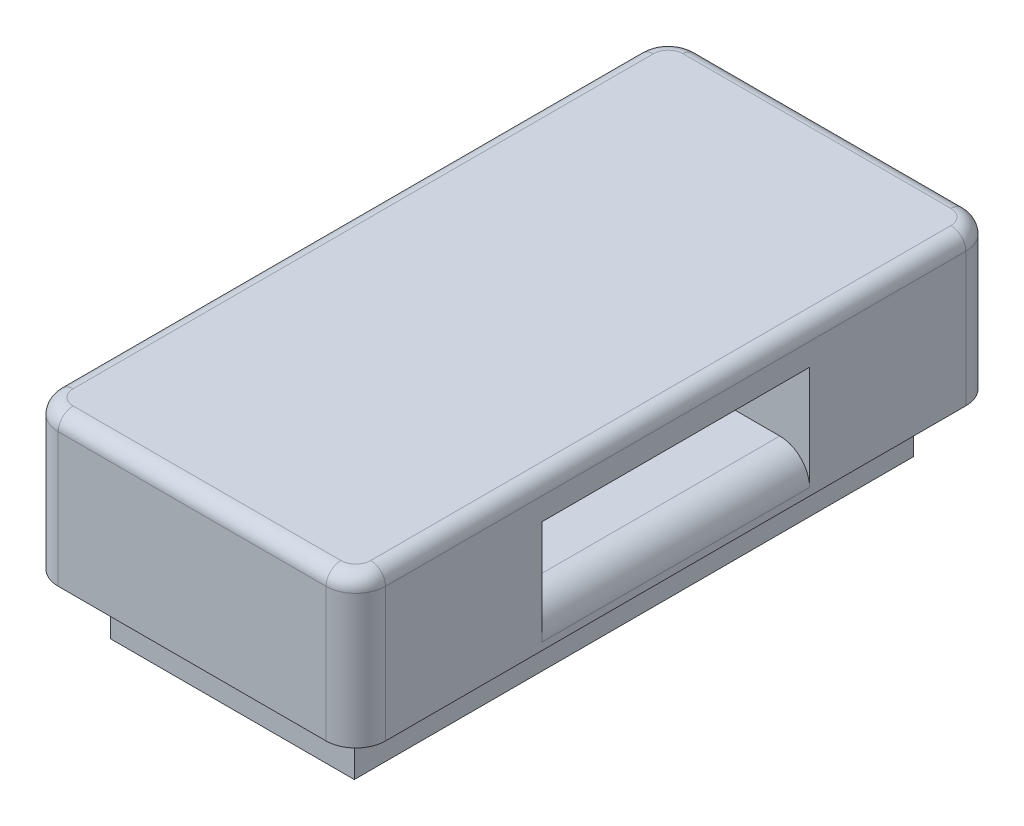
SolidWorks part; units mm, degrees
ref_plane "Front Plane" through (0, 0, 0) normal (0, 0, 1) x (1, 0, 0)
ref_plane "Top Plane" through (0, 0, 0) normal (0, 1, 0) x (1, 0, 0)
ref_plane "Right Plane" through (0, 0, 0) normal (1, 0, 0) x (0, 0, -1)
sketch "Sketch1" plane through (0, 0, 0) normal (0, 1, 0) x (1, 0, 0)
  line L1 (8.2, -18.8) -> (-8.2, -18.8)
  line L2 (8.2, -18.8) -> (8.2, 18.8)
  line L3 (8.2, 18.8) -> (-8.2, 18.8)
  line L4 (-8.2, -18.8) -> (-8.2, 18.8)
  line L5 (8.2, -18.8) -> (-8.2, 18.8) construction
  line L6 (8.2, 18.8) -> (-8.2, -18.8) construction
  line L7 (-9, -21.5) -> (9, -21.5)
  line L8 (-11, -19.5) -> (-11, 19.5)
  line L9 (-9, 21.5) -> (9, 21.5)
  line L10 (11, -19.5) -> (11, 19.5)
  line L11 (-11, -21.5) -> (11, 21.5) construction
  line L12 (-11, 21.5) -> (11, -21.5) construction
  arc A0 (-9, -21.5) -> (-11, -19.5) centre (-9, -19.5) cw
  arc A1 (9, -21.5) -> (11, -19.5) centre (9, -19.5) ccw
  arc A2 (9, 21.5) -> (11, 19.5) centre (9, 19.5) cw
  arc A3 (-11, 19.5) -> (-9, 21.5) centre (-9, 19.5) cw
  point P0 (0, 0)
  point P6 (0, 0)
  dimension "D5" = 2
  dimension "D1" = 16.4
  dimension "D2" = 37.6
  dimension "D3" = 22
  dimension "D4" = 43
extrude "Boss-Extrude1" add sketch "Sketch1" along normal blind 10 contours L9 A2 L10 A1 L7 A0 L8 A3
extrude "Boss-Extrude2" add sketch "Sketch1<4>" against normal blind 4 contours L4 L1 L2 L3 region at (0, 0, 0)
sketch "Sketch1<4>" plane through (0, 0, 0) normal (0, 1, 0) x (1, 0, 0) same geometry as "Sketch1"
sketch "Sketch3" plane through (-11, 0, 10.5) normal (1, 0, 0) x (0, 0, -1)
  line L1 (1.5, 7.5) -> (19.5, 7.5)
  line L2 (1.5, 7.5) -> (1.5, 2.5)
  line L3 (1.5, 2.5) -> (19.5, 2.5)
  line L4 (19.5, 7.5) -> (19.5, 2.5)
  line L6 (-9, 10) -> (30, 10) construction
  point P6 (10.5, 2.5)
  dimension "D1" = 18
  dimension "D2" = 5
  dimension "D3" = 2.5
extrude "Cut-Extrude2" cut sketch "Sketch3" along normal through all contours L4 L3 L2 L1
fillet "Fillet1" radius 2 2 edges at (11, 2.5, 0) (-11, 2.5, 0)
fillet "Fillet2" radius 1 8 edges at (-10.4142, 10, 20.9142) (-11, 10, 0) (-10.4142, 10, -20.9142) (0, 10, -21.5) (10.4142, 10, -20.9142) (11, 10, 0) (10.4142, 10, 20.9142) (0, 10, 21.5)
